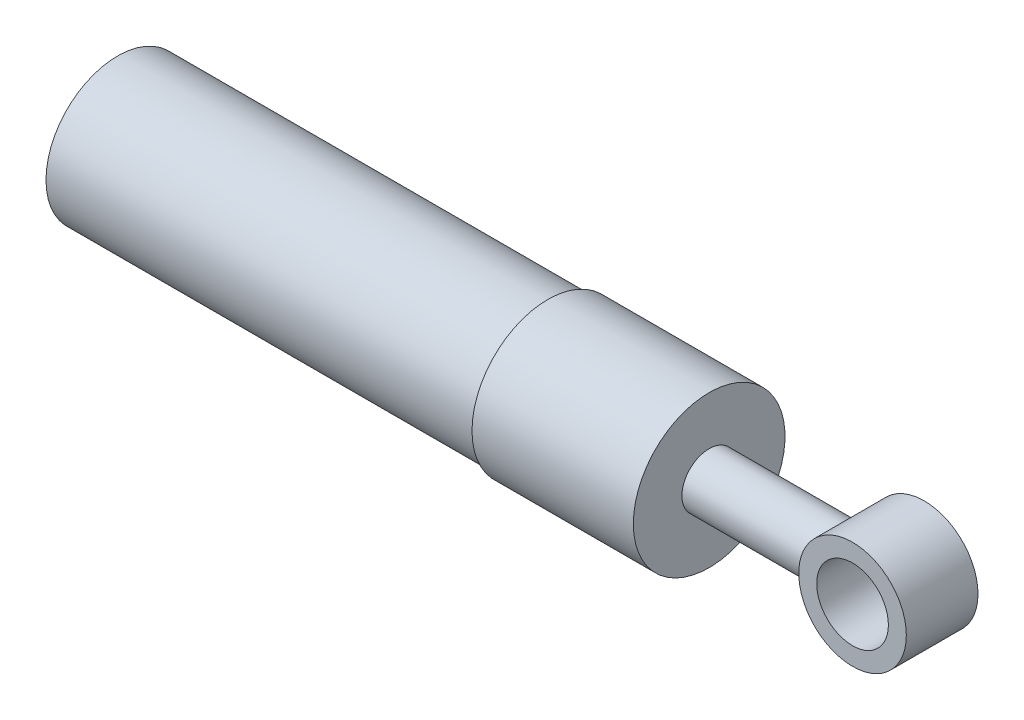
SolidWorks part; units mm, degrees
ref_plane "Front Plane" through (0, 0, 0) normal (0, 0, 1) x (1, 0, 0)
ref_plane "Top Plane" through (0, 0, 0) normal (0, 1, 0) x (1, 0, 0)
ref_plane "Right Plane" through (0, 0, 0) normal (1, 0, 0) x (0, 0, -1)
sketch "Sketch2" plane through (0, 0, 0) normal (0, 0, 1) x (1, 0, 0)
  line L0 (0, 0) -> (0, 6.35)
  line L1 (0, 6.35) -> (38.1, 6.35)
  line L2 (38.1, 6.35) -> (38.1, 6.7183)
  line L3 (38.1, 6.7183) -> (52.3875, 6.7183)
  line L4 (52.3875, 6.7183) -> (52.3875, 2.413)
  line L5 (52.3875, 2.413) -> (65.0875, 2.413)
  line L6 (65.0875, 2.413) -> (65.0875, 0)
  line L7 (0, 0) -> (65.0875, 0)
  dimension "D1" = 6.35
  dimension "D2" = 38.1
  dimension "D3" = 14.2875
  dimension "D4" = 12.7
  dimension "D5" = 6.7183
  dimension "D6" = 2.413
revolve "Revolve1" add sketch "Sketch2" angle 360 about L7
sketch "Sketch3" plane through (0, 0, 0) normal (0, 0, 1) x (1, 0, 0)
  line L0 (65.0875, -2.413) -> (65.0875, 2.413) construction
  circle A0 centre (68.2625, 0) radius 3.175
  circle A1 centre (68.2625, 0) radius 4.7625
  dimension "D1" = 1.5875
  dimension "D2" = 6.35
extrude "Boss-Extrude1" add sketch "Sketch3" along normal mid plane 6.35
